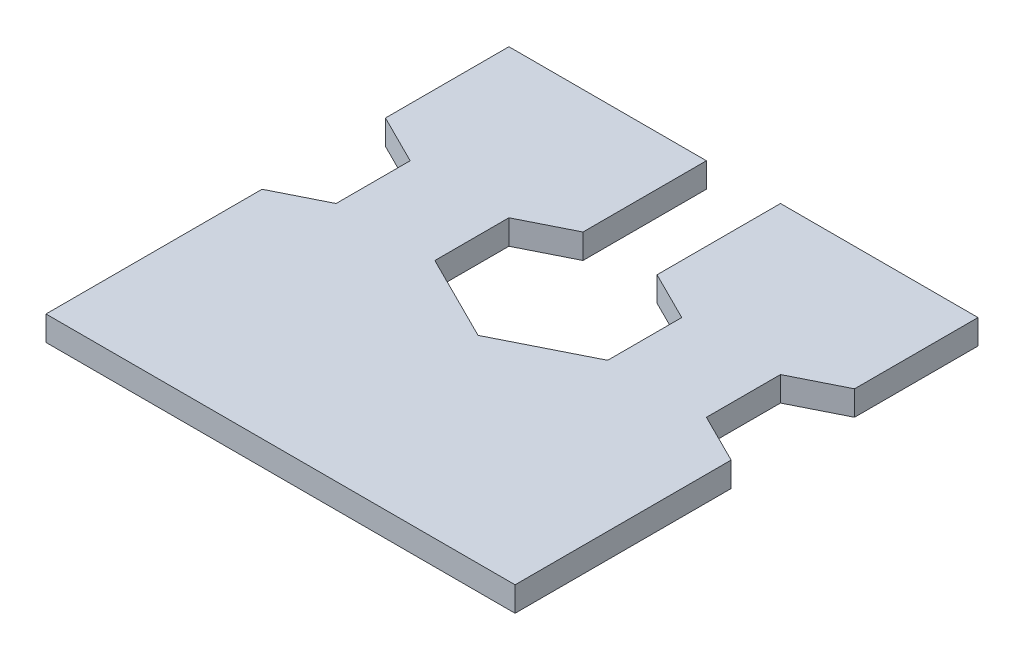
SolidWorks part; units mm, degrees
ref_plane "Plano frontal" through (0, 0, 0) normal (0, 0, 1) x (1, 0, 0)
ref_plane "Plano superior" through (0, 0, 0) normal (0, 1, 0) x (1, 0, 0)
ref_plane "Plano direito" through (0, 0, 0) normal (1, 0, 0) x (0, 0, -1)
sketch "Esboço1" plane through (0, 0, 0) normal (0, 1, 0) x (1, 0, 0)
  line L0 (3, 37.5008) -> (19, 37.5008)
  line L1 (19, 37.5008) -> (19, 27.5008)
  line L2 (19, 27.5008) -> (15, 25.5008)
  line L3 (15, 25.5008) -> (15, 19.5008)
  line L4 (15, 19.5008) -> (19, 17.5008)
  line L5 (19, 17.5008) -> (19, 0)
  line L6 (19, 0) -> (-19, 0)
  line L7 (3, 37.5008) -> (3, 27.5008)
  line L8 (3, 27.5008) -> (7, 25.5008)
  line L9 (7, 25.5008) -> (7, 19.5008)
  line L10 (7, 19.5008) -> (0, 16)
  line L11 (0, -6.2945) -> (0, 31.7121) construction
  line L13 (-7, 19.5008) -> (0, 16)
  line L14 (-7, 25.5008) -> (-7, 19.5008)
  line L15 (-3, 27.5008) -> (-7, 25.5008)
  line L16 (-3, 37.5008) -> (-3, 27.5008)
  line L17 (-19, 17.5008) -> (-19, 0)
  line L18 (-15, 19.5008) -> (-19, 17.5008)
  line L19 (-15, 25.5008) -> (-15, 19.5008)
  line L20 (-19, 27.5008) -> (-15, 25.5008)
  line L21 (-19, 37.5008) -> (-19, 27.5008)
  line L22 (-3, 37.5008) -> (-19, 37.5008)
  point P18 (0, 0)
  dimension "D1" = 6
  dimension "D2" = 2
  dimension "D3" = 2
  dimension "D4" = 4
  dimension "D5" = 16
  dimension "D6" = 4
  dimension "D7" = 19
  dimension "D8" = 116.57
  dimension "D9" = 16
  dimension "D10" = 10
base flange "Flange-base1" sketch "Esboço1" thickness 2 reverse thickness direction no parameters "D1"=0.7366
sketch "Curva-Linhas1" [suppressed] plane through (0, 0, 0) normal (0, 1, 0) x (1, 0, 0)
sketch "Caixa delimitadora1" [suppressed] plane through (0, 0, 0) normal (0, 1, 0) x (1, 0, 0)
sheet metal parameters "Chapa metálica1" thickness 2 parameters "D1"=0.7366
flat pattern "Padrão-Plano1" [suppressed]
sketch "Curva-Linhas2" plane through (0, 0, 0) normal (0, 1, 0) x (1, 0, 0)
sketch3d "Caixa delimitadora2" [suppressed]
  line L0 (19, 0, 0) -> (-19, 0, 0) construction
  line L1 (19, 37.5008, 0) -> (-19, 37.5008, 0) construction
  line L2 (19, 0, 0) -> (19, 37.5008, 0) construction
  line L3 (-19, 0, 0) -> (-19, 37.5008, 0) construction
